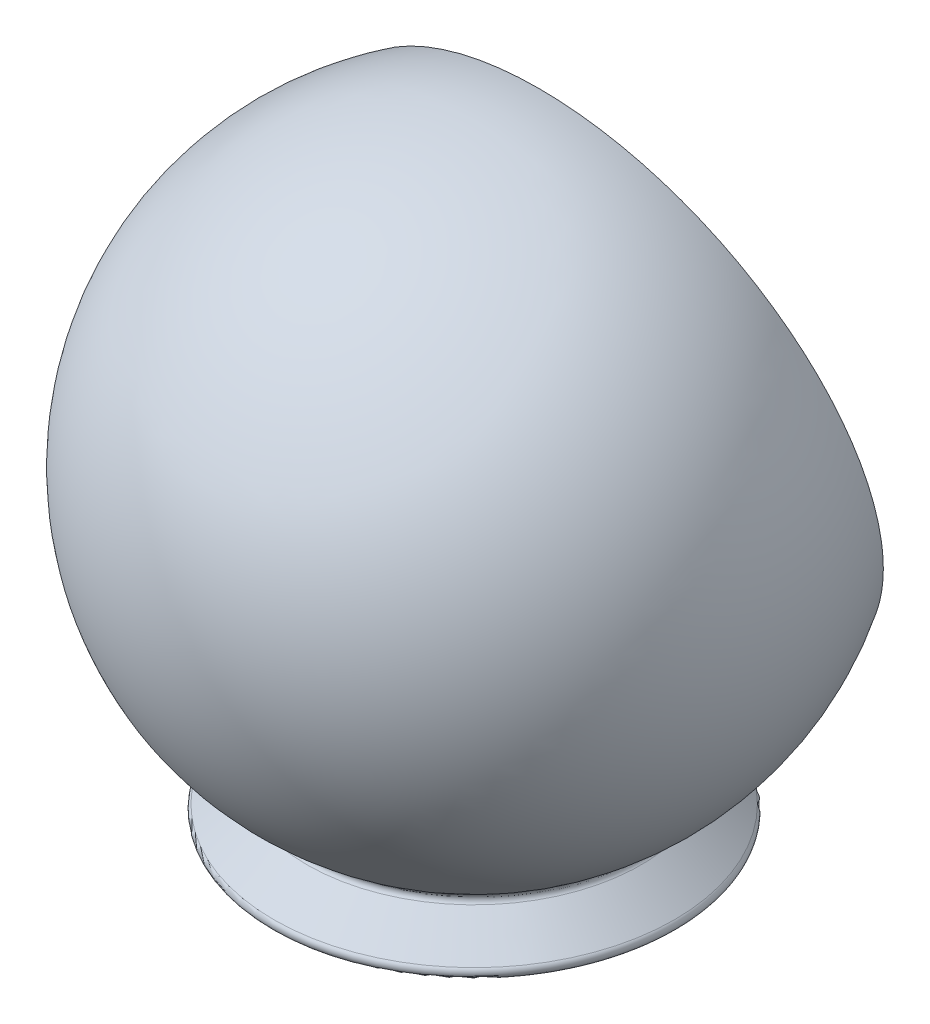
SolidWorks part; units mm, degrees
ref_plane "Front Plane" through (0, 0, 0) normal (0, 0, 1) x (1, 0, 0)
ref_plane "Top Plane" through (0, 0, 0) normal (0, 1, 0) x (1, 0, 0)
ref_plane "Right Plane" through (0, 0, 0) normal (1, 0, 0) x (0, 0, -1)
sketch "Base_sketch" plane through (0, 0, 0) normal (0, 1, 0) x (1, 0, 0)
  line L0 (0, 63.5) -> (0, -63.5)
  line L2 (0, -69.85) -> (0, 69.85) construction
  arc A0 (0, 63.5) -> (0, -63.5) centre (0, 0) cw
  point P7 (0, 0)
  dimension "D2" = 63.5
  dimension "D1" = 127
revolve "Revolve2" add sketch "Base_sketch" angle 360 about L0
ref_plane "Plane3" through (0, -48.26, 0) normal (0, 1, 0) x (1, 0, 0)
ref_plane "Plane4" through (0, -63.5, 0) normal (0, 1, 0) x (1, 0, 0)
sketch "Sketch8" plane through (0, -48.26, 0) normal (0, 1, 0) x (1, 0, 0)
  circle A0 centre (0, 0) radius 27.942
  dimension "D1" = 55.884
sketch "Sketch9" plane through (0, -63.5, 0) normal (0, 1, 0) x (1, 0, 0)
  circle A0 centre (0, 0) radius 44.45
  dimension "D1" = 88.9
loft "Loft1" add profiles "Sketch8", "Sketch9" connector at (-15.5018, -48.26, -23.2476) connector at (-26.5993, -63.5, -35.6129)
combine bodies "Combine1" operation type add bodies to combine 105 104
fillet "Fillet2" radius 1.27 1 edges at (0, -53.7209, 33.8573)
fillet "Fillet3" radius 1.27 1 edges at (0, -63.5, 44.45)
sketch "Sketch10" plane through (0, -48.26, 0) normal (0, 1, 0) x (1, 0, 0)
  line L0 (37.2305, 41.1538) -> (-37.2305, 41.1538)
  circle A0 centre (0, 0) radius 41.1538
  point P6 (0, 41.1538)
ref_plane "Plane5" through (0, 6.8358, -27.4169) normal (0, 0.2419, -0.9703) x (-1, 0, 0)
sketch "Sketch11" plane through (0, 6.8358, -27.4169) normal (0, 0.2419, -0.9703) x (-1, 0, 0)
  line L1 (-68.0843, 65.2783) -> (67.1582, 65.2783)
  line L2 (-68.0843, 65.2783) -> (-68.0843, -59.9167)
  line L3 (-68.0843, -59.9167) -> (67.1582, -59.9167)
  line L4 (67.1582, 65.2783) -> (67.1582, -59.9167)
sketch "Sketch12" plane through (0, 6.8358, -27.4169) normal (0, 0.2419, -0.9703) x (-1, 0, 0)
  line L0 (0, 57.3739) -> (0, -56.7825) construction
  line L1 (57.3739, 0) -> (-57.3739, 0) construction
  circle A0 centre (0, 0) radius 57.3739
  circle A1 centre (0, 0) radius 51.5188
  dimension "D1" = 114.7478
  dimension "D2" = 103.0375
extrude "Cut-Extrude1" cut sketch "Sketch12" along normal blind 38.1 contours A1 | A0 A1 region at (55.7511, 6.8358, -27.4169) region at (0, 6.8358, -27.4169)
